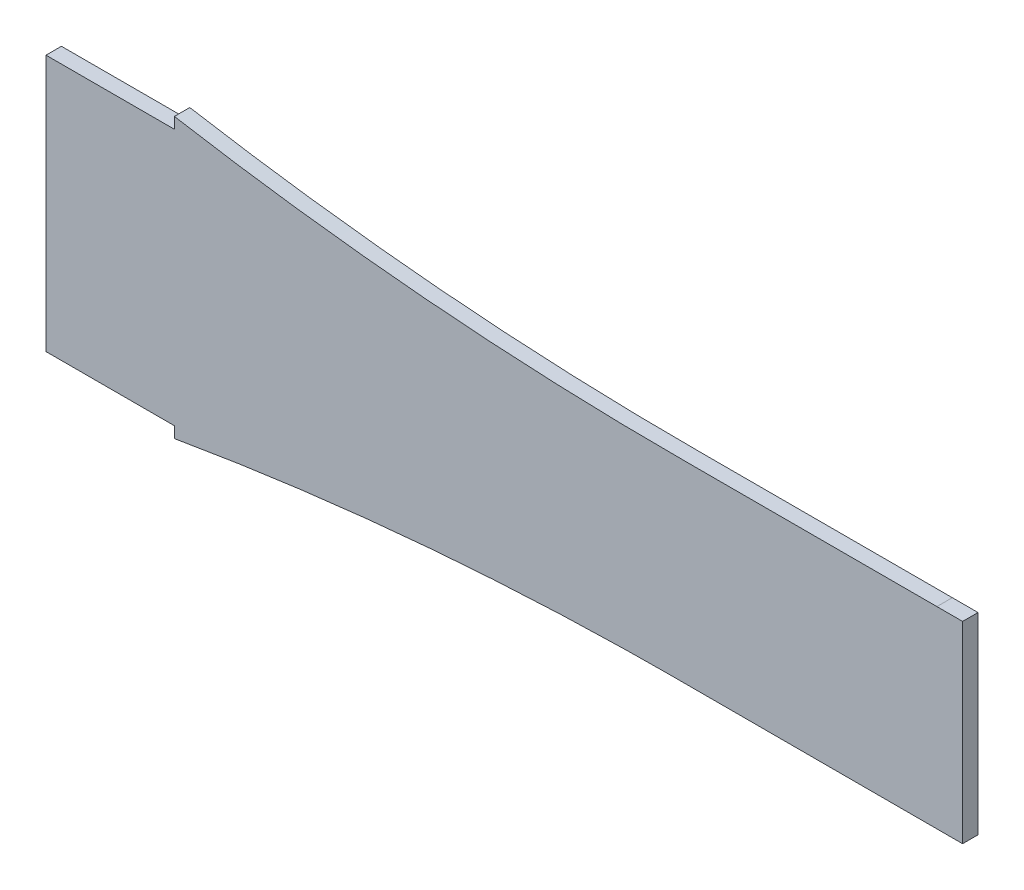
SolidWorks part; units mm, degrees
ref_plane "Front Plane" through (0, 0, 0) normal (0, 0, 1) x (1, 0, 0)
ref_plane "Top Plane" through (0, 0, 0) normal (0, 1, 0) x (1, 0, 0)
ref_plane "Right Plane" through (0, 0, 0) normal (1, 0, 0) x (0, 0, -1)
sketch "Sketch2" plane through (0, 0, 0) normal (0, 0, 1) x (1, 0, 0)
  line L0 (200.5037, 13.5) -> (209.6614, 13.5)
  line L1 (209.6614, 13.5) -> (209.6614, -1.5)
  line L2 (209.6614, -1.5) -> (200.5037, -1.5)
  line L3 (200.5037, 14.5) -> (200.5037, -2.5) construction
  line L4 (141.1014, -5.8814) -> (141.1014, 17.8814)
  line L5 (141.1014, -5.8703) -> (141.1014, 17.8703) construction
  line L6 (141.1014, 6) -> (131.1014, 6) construction
  line L7 (131.1014, -4) -> (131.1014, 16)
  line L8 (131.1014, 16) -> (141.1014, 16)
  line L9 (131.1014, -4) -> (141.1014, -4)
  line L10 (200.5037, 6) -> (200.5037, 14.5) construction
  line L11 (202.5037, 13.5) -> (202.5037, -1.5)
  spline S0 degree 3 poles (-60772.6174, 14.4999) (3271.304, 14.5) (1651.3151, 14.5) (196.3269, 14.5) (193.888, 14.5) (191.0728, 14.5) (187.3121, 14.5) (184.7957, 14.5) (183.1316, 14.5) (181.6678, 14.5) (180.8042, 14.5) (176.6959, 14.5) (170.0157, 14.6701) (160.6834, 15.2826) (151.3787, 16.2729) (144.7571, 17.2475) (137.0942, 18.5762) (128.7706, 20.2388) (115.6154, 23.6651) (102.2952, 28.0145) (93.7289, 31.4059) (87.8309, 33.9398) (84.2733, 35.4453) (78.9172, 37.6421) (73.5322, 39.779) (69.9169, 41.1646) (62.947, 43.787) (52.5705, 47.4882) (36.8074, 52.4484) (20.8512, 56.7586) (4.7163, 60.345) (-11.5784, 63.1299) (-28.0024, 65.0223) (-41.7611, 65.7726) (-52.7809, 65.8211) (-61.0417, 65.5664) (-69.2882, 65.0054) (-77.5061, 64.1216) (-85.6813, 62.8986) (-93.7948, 61.3187) (-101.8273, 59.3643) (-109.7537, 57.0167) (-117.5469, 54.2566) (-125.1734, 51.0636) (-132.5939, 47.4161) (-139.7605, 43.2898) (-146.6112, 38.6566) (-153.0658, 33.4818) (-158.0148, 28.68) (-161.625, 24.512) (-164.1129, 21.2106) (-166.3358, 17.722) (-168.204, 14.0278) (-208.7676, -101.1332) (701.5353, -482.4231) (57920.4232, 17972.9355) knots -7.799673 -7.799673 -7.799673 -7.799673 0.019555 0.026074 0.026074 0.032675 0.039275 0.042576 0.045876 0.049176 0.052477 0.052477 0.082322 0.112168 0.142014 0.17186 0.17186 0.204575 0.23729 0.270005 0.30272 0.30272 0.316827 0.330935 0.345042 0.359149 0.359149 0.399202 0.439255 0.479309 0.519362 0.559415 0.599468 0.639521 0.659548 0.679575 0.699601 0.719628 0.739654 0.759681 0.779707 0.799734 0.819761 0.839787 0.859814 0.87984 0.899867 0.919894 0.93992 0.949934 0.959947 0.96996 0.979973 0.989987 1.855568 1.855568 1.855568 1.855568 only from (200.5037, 14.5) to (-170, 6) construction
  spline S1 degree 3 poles (200.5037, 14.5) (199.9194, 14.5) (198.123, 14.5) (196.3269, 14.5) (193.888, 14.5) (191.0728, 14.5) (187.3121, 14.5) (184.7957, 14.5) (183.1316, 14.5) (181.6678, 14.5) (180.8042, 14.5) (176.6959, 14.5) (170.0157, 14.6701) (160.6834, 15.2826) (151.3787, 16.2729) (144.7571, 17.2475) (137.0942, 18.5762) (128.7706, 20.2388) (115.6154, 23.6651) (102.2952, 28.0145) (93.7289, 31.4059) (87.8309, 33.9398) (84.2733, 35.4453) (78.9172, 37.6421) (73.5322, 39.779) (69.9169, 41.1646) (62.947, 43.787) (52.5705, 47.4882) (36.8074, 52.4484) (20.8512, 56.7586) (4.7163, 60.345) (-11.5784, 63.1299) (-28.0024, 65.0223) (-41.7611, 65.7726) (-52.7809, 65.8211) (-61.0417, 65.5664) (-69.2882, 65.0054) (-77.5061, 64.1216) (-85.6813, 62.8986) (-93.7948, 61.3187) (-101.8273, 59.3643) (-109.7537, 57.0167) (-117.5469, 54.2566) (-125.1734, 51.0636) (-132.5939, 47.4161) (-139.7605, 43.2898) (-146.6112, 38.6566) (-153.0658, 33.4818) (-158.0148, 28.68) (-161.625, 24.512) (-164.1129, 21.2106) (-166.3358, 17.722) (-168.204, 14.0278) (-169.5799, 10.1215) (-170, 7.3775) (-170, 6) knots 0.016413 0.016413 0.016413 0.016413 0.019555 0.026074 0.026074 0.032675 0.039275 0.042576 0.045876 0.049176 0.052477 0.052477 0.082322 0.112168 0.142014 0.17186 0.17186 0.204575 0.23729 0.270005 0.30272 0.30272 0.316827 0.330935 0.345042 0.359149 0.359149 0.399202 0.439255 0.479309 0.519362 0.559415 0.599468 0.639521 0.659548 0.679575 0.699601 0.719628 0.739654 0.759681 0.779707 0.799734 0.819761 0.839787 0.859814 0.87984 0.899867 0.919894 0.93992 0.949934 0.959947 0.96996 0.979973 0.989987 1 1 1 1
  spline S2 degree 3 poles (-60772.6172, -2.5) (3271.304, -2.5) (1651.3151, -2.5) (196.3269, -2.5) (193.888, -2.5) (191.0728, -2.5) (187.3121, -2.5) (184.7957, -2.5) (183.1316, -2.5) (181.6678, -2.5) (180.8042, -2.5) (176.6959, -2.5) (170.0157, -2.6701) (160.6834, -3.2826) (151.3787, -4.2729) (144.7571, -5.2475) (137.0942, -6.5762) (128.7706, -8.2388) (115.6154, -11.6651) (102.2952, -16.0145) (93.7289, -19.4059) (87.8309, -21.9398) (84.2733, -23.4453) (78.9172, -25.6421) (73.5322, -27.779) (69.9169, -29.1646) (62.947, -31.787) (52.5705, -35.4882) (36.8074, -40.4484) (20.8512, -44.7586) (4.7163, -48.345) (-11.5784, -51.1299) (-28.0024, -53.0223) (-41.7611, -53.7726) (-52.7809, -53.8211) (-61.0417, -53.5664) (-69.2882, -53.0054) (-77.5061, -52.1216) (-85.6813, -50.8986) (-93.7948, -49.3187) (-101.8273, -47.3643) (-109.7537, -45.0167) (-117.5469, -42.2566) (-125.1734, -39.0636) (-132.5939, -35.4161) (-139.7605, -31.2898) (-146.6112, -26.6566) (-153.0658, -21.4818) (-158.0148, -16.68) (-161.625, -12.512) (-164.1129, -9.2106) (-166.3358, -5.722) (-168.204, -2.0278) (-208.7676, 113.1332) (701.5353, 494.4231) (57920.4232, -17960.9355) knots -7.799673 -7.799673 -7.799673 -7.799673 0.019555 0.026074 0.026074 0.032675 0.039275 0.042576 0.045876 0.049176 0.052477 0.052477 0.082322 0.112168 0.142014 0.17186 0.17186 0.204575 0.23729 0.270005 0.30272 0.30272 0.316827 0.330935 0.345042 0.359149 0.359149 0.399202 0.439255 0.479309 0.519362 0.559415 0.599468 0.639521 0.659548 0.679575 0.699601 0.719628 0.739654 0.759681 0.779707 0.799734 0.819761 0.839787 0.859814 0.87984 0.899867 0.919894 0.93992 0.949934 0.959947 0.96996 0.979973 0.989987 1.855568 1.855568 1.855568 1.855568 only from (200.5037, -2.5) to (-170, 6) construction
  spline S3 degree 3 poles (200.5037, -2.5) (199.9194, -2.5) (198.123, -2.5) (196.3269, -2.5) (193.888, -2.5) (191.0728, -2.5) (187.3121, -2.5) (184.7957, -2.5) (183.1316, -2.5) (181.6678, -2.5) (180.8042, -2.5) (176.6959, -2.5) (170.0157, -2.6701) (160.6834, -3.2826) (151.3787, -4.2729) (144.7571, -5.2475) (137.0942, -6.5762) (128.7706, -8.2388) (115.6154, -11.6651) (102.2952, -16.0145) (93.7289, -19.4059) (87.8309, -21.9398) (84.2733, -23.4453) (78.9172, -25.6421) (73.5322, -27.779) (69.9169, -29.1646) (62.947, -31.787) (52.5705, -35.4882) (36.8074, -40.4484) (20.8512, -44.7586) (4.7163, -48.345) (-11.5784, -51.1299) (-28.0024, -53.0223) (-41.7611, -53.7726) (-52.7809, -53.8211) (-61.0417, -53.5664) (-69.2882, -53.0054) (-77.5061, -52.1216) (-85.6813, -50.8986) (-93.7948, -49.3187) (-101.8273, -47.3643) (-109.7537, -45.0167) (-117.5469, -42.2566) (-125.1734, -39.0636) (-132.5939, -35.4161) (-139.7605, -31.2898) (-146.6112, -26.6566) (-153.0658, -21.4818) (-158.0148, -16.68) (-161.625, -12.512) (-164.1129, -9.2106) (-166.3358, -5.722) (-168.204, -2.0278) (-169.5799, 1.8785) (-170, 4.6225) (-170, 6) knots 0.016413 0.016413 0.016413 0.016413 0.019555 0.026074 0.026074 0.032675 0.039275 0.042576 0.045876 0.049176 0.052477 0.052477 0.082322 0.112168 0.142014 0.17186 0.17186 0.204575 0.23729 0.270005 0.30272 0.30272 0.316827 0.330935 0.345042 0.359149 0.359149 0.399202 0.439255 0.479309 0.519362 0.559415 0.599468 0.639521 0.659548 0.679575 0.699601 0.719628 0.739654 0.759681 0.779707 0.799734 0.819761 0.839787 0.859814 0.87984 0.899867 0.919894 0.93992 0.949934 0.959947 0.96996 0.979973 0.989987 1 1 1 1
  spline S4 degree 1 poles (200.5037, 13.5) (-169, 6) knots 0 0 1 1 construction
  spline S5 degree 1 poles (200.5037, -1.5) (-169, 6) knots 0 0 1 1 construction
  spline S6 degree 3 poles (200.5037, 13.5) (199.0749, 13.5) (196.9227, 13.5) (194.0893, 13.5) (191.6341, 13.5) (189.0477, 13.5) (185.72, 13.5) (183.0676, 13.5) (180.929, 13.5) (179.0487, 13.5001) (176.7365, 13.5231) (174.0919, 13.5803) (171.5277, 13.6658) (169.0252, 13.7763) (165.7406, 13.9552) (161.7091, 14.2399) (156.9004, 14.6804) (152.0265, 15.232) (147.0149, 15.9034) (141.6483, 16.7494) (135.8521, 17.8088) (127.9548, 19.4662) (117.6626, 22.0526) (105.0957, 25.988) (94.8316, 29.8422) (87.0595, 33.19) (79.3241, 36.4198) (69.5591, 40.2856) (57.6652, 44.6375) (45.6694, 48.6476) (29.5187, 53.5135) (9.0569, 58.6198) (-15.8793, 62.9176) (-41.0872, 65.0643) (-66.3795, 64.6809) (-91.4465, 61.3301) (-111.7458, 55.6595) (-127.2357, 49.1261) (-138.3275, 43.1511) (-148.6984, 36.0118) (-158.0272, 27.5946) (-164.4962, 19.3623) (-167.6539, 12.8663) (-168.7689, 8.9528) (-169, 6.9892) (-169, 6) knots 0.016413 0.016413 0.016413 0.016413 0.024098 0.02794 0.031782 0.035624 0.039466 0.04715 0.050992 0.054835 0.062519 0.070203 0.077887 0.085572 0.093256 0.108624 0.123993 0.139362 0.15473 0.170099 0.185467 0.200836 0.231573 0.26231 0.293047 0.308416 0.323784 0.354521 0.385258 0.415995 0.446732 0.508207 0.569681 0.631155 0.692629 0.754103 0.815577 0.846315 0.877052 0.907789 0.938526 0.969263 0.984631 0.992316 1 1 1 1
  spline S7 degree 3 poles (-169, 6) (-169, 5.0108) (-168.7689, 3.0472) (-167.6539, -0.8663) (-164.4962, -7.3623) (-158.0272, -15.5946) (-148.6984, -24.0118) (-138.3275, -31.1511) (-127.2357, -37.1261) (-111.7458, -43.6595) (-91.4465, -49.3301) (-66.3795, -52.6809) (-41.0872, -53.0643) (-15.8793, -50.9176) (9.0569, -46.6198) (29.5187, -41.5135) (45.6694, -36.6476) (57.6652, -32.6375) (69.5591, -28.2856) (79.3241, -24.4198) (87.0595, -21.19) (94.8316, -17.8422) (105.0957, -13.988) (117.6626, -10.0526) (127.9548, -7.4662) (135.8521, -5.8088) (141.6483, -4.7494) (147.0149, -3.9034) (152.0265, -3.232) (156.9004, -2.6804) (161.7091, -2.2399) (165.7406, -1.9552) (169.0252, -1.7763) (171.5277, -1.6658) (174.0919, -1.5803) (176.7365, -1.5231) (179.0487, -1.5001) (180.929, -1.5) (183.0676, -1.5) (185.72, -1.5) (189.0477, -1.5) (191.6341, -1.5) (194.0893, -1.5) (196.9227, -1.5) (199.0749, -1.5) (200.5037, -1.5) knots 0.016413 0.016413 0.016413 0.016413 0.024098 0.031782 0.04715 0.077887 0.108624 0.139362 0.170099 0.200836 0.26231 0.323784 0.385258 0.446732 0.508207 0.569681 0.600418 0.631155 0.661892 0.692629 0.707998 0.723366 0.754103 0.78484 0.815577 0.830946 0.846315 0.861683 0.877052 0.89242 0.907789 0.923157 0.930842 0.938526 0.94621 0.953894 0.961579 0.965421 0.969263 0.976947 0.980789 0.984631 0.988474 0.992316 1 1 1 1
  spline S8 degree 3 poles (200.5037, 14.5) (199.9194, 14.5) (198.123, 14.5) (196.3269, 14.5) (193.888, 14.5) (191.0728, 14.5) (187.3121, 14.5) (184.7957, 14.5) (183.1316, 14.5) (181.6678, 14.5) (180.8042, 14.5) (176.6959, 14.5) (170.0157, 14.6701) (160.6834, 15.2826) (151.3787, 16.2729) (144.7571, 17.2475) (137.0942, 18.5762) (128.7706, 20.2388) (115.6154, 23.6651) (102.2952, 28.0145) (93.7289, 31.4059) (87.8309, 33.9398) (84.2733, 35.4453) (78.9172, 37.6421) (73.5322, 39.779) (69.9169, 41.1646) (64.7821, 43.0966) (61.4486, 44.3087) (58.1014, 45.4814) knots 0.016413 0.016413 0.016413 0.016413 0.019555 0.026074 0.026074 0.032675 0.039275 0.042576 0.045876 0.049176 0.052477 0.052477 0.082322 0.112168 0.142014 0.17186 0.17186 0.204575 0.23729 0.270005 0.30272 0.30272 0.316827 0.330935 0.345042 0.359149 0.359149 0.384943 0.384943 0.384943 0.384943 construction
  point P20 (131.1014, 6)
  dimension "D2" = 10
  dimension "D3" = 20
  dimension "D4" = 2
  dimension "D1" = 1
extrude "Boss-Extrude1" add sketch "Sketch2" along normal blind 0.6 and the other way blind 0.6 contours L4 S7 L2 L1 L0 S6 | L7 L9 L4 L8 region at (169.9819, 6, 0) region at (136.1014, 6, 0)
sketch "Sketch3" plane through (0, 0, 0) normal (0, 0, 1) x (1, 0, 0)
  line L0 (196.3938, 6) -> (20, 6) construction
  line L1 (68.1014, -4) -> (134.1014, -4)
  line L2 (68.1014, -4) -> (68.1014, 16)
  line L3 (68.1014, 16) -> (134.1014, 16)
  line L4 (134.1014, -4) -> (134.1014, 16)
  line L5 (68.1014, -4) -> (134.1014, 16) construction
  line L6 (68.1014, 16) -> (134.1014, -4) construction
  line L7 (134.1014, -7.1964) -> (134.1014, 19.1964) construction
  line L8 (68.1014, 41.8477) -> (68.1014, 6) construction
  circle A0 centre (73.1014, 12.3713) radius 1.6 construction
  circle A1 centre (73.1014, -0.3713) radius 1.6 construction
  circle A2 centre (93.1014, 0.6287) radius 1.6 construction
  circle A3 centre (93.1014, 11.3713) radius 1.6 construction
  circle A4 centre (131.6014, 0.6287) radius 1.6 construction
  circle A5 centre (131.6014, 11.3713) radius 1.6 construction
  circle A6 centre (113.1014, 0.6287) radius 1.6 construction
  circle A7 centre (113.1014, 11.3713) radius 1.6 construction
  circle A8 centre (73.1014, 12.3713) radius 1.6
  circle A9 centre (73.1014, -0.3713) radius 1.6
  circle A10 centre (93.1014, 0.6287) radius 1.6
  circle A11 centre (93.1014, 11.3713) radius 1.6
  circle A12 centre (131.6014, 0.6287) radius 1.6
  circle A13 centre (131.6014, 11.3713) radius 1.6
  circle A14 centre (113.1014, 0.6287) radius 1.6
  circle A15 centre (113.1014, 11.3713) radius 1.6
  point P0 (101.1014, 6)
  dimension "D1" = 20
sketch "Sketch4" plane through (0, 0, 0) normal (0, 0, 1) x (1, 0, 0)
  circle A0 centre (138.6014, 11.3713) radius 1.6 construction
  circle A1 centre (138.6014, 11.3713) radius 1.6
  circle A2 centre (138.6014, 0.6287) radius 1.6 construction
  circle A3 centre (138.6014, 0.6287) radius 1.6
